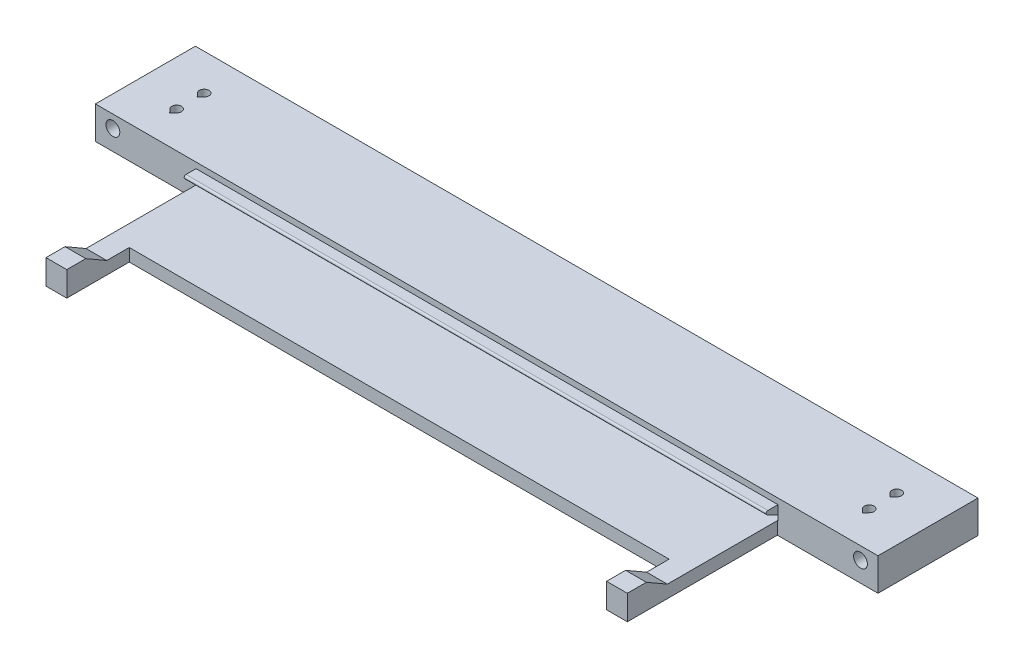
SolidWorks part; units mm, degrees
ref_plane "Front Plane" through (0, 0, 0) normal (0, 0, 1) x (1, 0, 0)
ref_plane "Top Plane" through (0, 0, 0) normal (0, 1, 0) x (1, 0, 0)
ref_plane "Right Plane" through (0, 0, 0) normal (1, 0, 0) x (0, 0, -1)
sketch "Sketch1" plane through (0, 0, 0) normal (1, 0, 0) x (0, 0, -1)
  line L1 (0, 0) -> (40, 0)
  line L2 (0, 0) -> (0, 10)
  line L3 (0, 10) -> (40, 10)
  line L4 (40, 0) -> (40, 10)
  dimension "D1" = 10
  dimension "D2" = 40
extrude "Boss-Extrude1" add sketch "Sketch1" along normal blind 312.998
sketch "Sketch2" plane through (0, 0, -40) normal (0, 0, -1) x (-1, 0, 0)
  line L1 (-272.994, 3) -> (-40.004, 3)
  line L2 (-272.994, 3) -> (-272.994, 4.2)
  line L3 (-272.994, 4.2) -> (-40.004, 4.2)
  line L4 (-40.004, 3) -> (-40.004, 4.2)
  line L5 (-272.994, 4.2) -> (-312.998, 0) construction
  line L6 (-40.004, 4.2) -> (0, 0) construction
  line L7 (-312.998, 0) -> (0, 0) construction
  dimension "D1" = 232.99
  dimension "D2" = 3
  dimension "D3" = 1.2
extrude "Cut-Extrude1" cut sketch "Sketch2" against normal through all
sketch "Sketch3" plane through (0, 10, 0) normal (0, 1, 0) x (1, 0, 0)
  line L0 (156.499, 71.4665) -> (156.499, -49.9307) construction
  line L1 (0, 40) -> (156.499, 71.4665) construction
  line L2 (156.499, 71.4665) -> (312.998, 40) construction
  line L3 (312.998, 40) -> (312.998, 0) construction
  line L4 (312.998, 40) -> (0, 40) construction
  line L5 (312.998, 40) -> (294.998, 25.5) construction
  line L6 (294.998, 25.5) -> (294.998, 14.5) construction
  line L7 (294.998, 14.5) -> (312.998, 0) construction
  circle A0 centre (294.998, 25.5) radius 1.9177
  circle A1 centre (294.998, 14.5) radius 1.9177
  circle A2 centre (18, 14.5) radius 1.9177
  circle A3 centre (18, 25.5) radius 1.9177
  dimension "D3" = 3.8354
  dimension "D1" = 18
  dimension "D2" = 14.5
extrude "Cut-Extrude2" cut sketch "Sketch3" against normal through all
sketch "Sketch4" plane through (0, 0, 0) normal (0, -1, 0) x (1, 0, 0)
  line L1 (14.5837, -12.5276) -> (14.5837, -16.4724)
  line L2 (14.5837, -16.4724) -> (18, -18.4448)
  line L3 (18, -18.4448) -> (21.4163, -16.4724)
  line L4 (21.4163, -16.4724) -> (21.4163, -12.5276)
  line L5 (21.4163, -12.5276) -> (18, -10.5552)
  line L6 (18, -10.5552) -> (14.5837, -12.5276)
  line L7 (14.5837, -23.5276) -> (14.5837, -27.4724)
  line L8 (14.5837, -27.4724) -> (18, -29.4448)
  line L9 (18, -29.4448) -> (21.4163, -27.4724)
  line L10 (21.4163, -27.4724) -> (21.4163, -23.5276)
  line L11 (21.4163, -23.5276) -> (18, -21.5552)
  line L12 (18, -21.5552) -> (14.5837, -23.5276)
  line L13 (298.4143, -12.5276) -> (294.998, -10.5552)
  line L14 (294.998, -10.5552) -> (291.5817, -12.5276)
  line L15 (291.5817, -12.5276) -> (291.5817, -16.4724)
  line L16 (291.5817, -16.4724) -> (294.998, -18.4448)
  line L17 (294.998, -18.4448) -> (298.4143, -16.4724)
  line L18 (298.4143, -16.4724) -> (298.4143, -12.5276)
  line L19 (291.5817, -23.5276) -> (291.5817, -27.4724)
  line L20 (291.5817, -27.4724) -> (294.998, -29.4448)
  line L21 (294.998, -29.4448) -> (298.4143, -27.4724)
  line L22 (298.4143, -27.4724) -> (298.4143, -23.5276)
  line L23 (298.4143, -23.5276) -> (294.998, -21.5552)
  line L24 (294.998, -21.5552) -> (291.5817, -23.5276)
  circle A0 centre (18, -14.5) radius 3.4163 construction
  circle A1 centre (18, -25.5) radius 3.4163 construction
  circle A2 centre (294.998, -14.5) radius 3.4163 construction
  circle A3 centre (294.998, -25.5) radius 3.4163 construction
  dimension "D1" = 6.8326
extrude "Cut-Extrude3" cut sketch "Sketch4" against normal blind 4.3
sketch "Sketch5" plane through (0, 0, 0) normal (0, 0, 1) x (1, 0, 0)
  line L0 (0, 10) -> (7, 5) construction
  line L1 (7, 5) -> (0, 0) construction
  line L2 (0, 10) -> (156.499, 87.0064) construction
  line L3 (156.499, 87.0064) -> (312.998, 10) construction
  line L4 (312.998, 10) -> (312.998, 0) construction
  line L5 (312.998, 10) -> (0, 10) construction
  line L6 (156.499, 87.0064) -> (156.499, -80.9825) construction
  line L7 (305.998, 5) -> (312.998, 0) construction
  line L8 (312.998, 10) -> (305.998, 5) construction
  circle A0 centre (7, 5) radius 2.7623
  circle A1 centre (305.998, 5) radius 2.7623
  dimension "D1" = 5.5245
  dimension "D2" = 7
extrude "Cut-Extrude4" cut sketch "Sketch5" against normal through all
sketch "Sketch6" plane through (0, 0, 0) normal (-1, 0, 0) x (0, 0, 1)
  line L0 (-40, 10) -> (-33, 8.4163) construction
  line L1 (-33, 8.4163) -> (-29, 8.4163)
  line L2 (-33, 8.4163) -> (-33, 1.5837)
  line L3 (-33, 1.5837) -> (-29, 1.5837)
  line L4 (-29, 8.4163) -> (-29, 1.5837)
  line L9 (-33, 1.5837) -> (-40, 0) construction
  line L10 (-40, 10) -> (-20, 18.9404) construction
  line L11 (-20, 18.9404) -> (0, 10) construction
  line L12 (-20, 18.9404) -> (-20, -7.3414) construction
  line L13 (-7, 1.5837) -> (0, 0) construction
  line L14 (0, 10) -> (-7, 8.4163) construction
  line L15 (-11, 8.4163) -> (-11, 1.5837)
  line L16 (-7, 1.5837) -> (-11, 1.5837)
  line L17 (-7, 8.4163) -> (-7, 1.5837)
  line L18 (-7, 8.4163) -> (-11, 8.4163)
  dimension "D1" = 7
  dimension "D2" = 4
  dimension "D3" = 6.8326
extrude "Cut-Extrude5" cut sketch "Sketch6" against normal blind 15
ref_plane "Plane1" through (156.499, 0, 0) normal (-1, 0, 0) x (0, 0, 1)
sketch "Sketch7" plane through (0, 0, 0) normal (0, 0, 1) x (1, 0, 0)
  line L0 (312.998, 0) -> (0, 0) construction
  line L1 (40.249, 0) -> (272.749, 0)
  line L2 (40.249, 0) -> (40.249, 2.0463)
  line L3 (40.249, 2.0463) -> (272.749, 2.0463)
  line L4 (272.749, 0) -> (272.749, 2.0463)
  line L5 (40.249, 2.0463) -> (40.004, 4.2) construction
  line L6 (272.994, 4.2) -> (272.749, 2.0463) construction
  dimension "D1" = 232.5
extrude "Boss-Extrude2" add sketch "Sketch7" along normal blind 60
sketch "Sketch8" plane through (0, 2.0463, 0) normal (0, 1, 0) x (1, 0, 0)
  line L0 (272.749, -60) -> (40.249, -60) construction
  line L1 (48.549, -35) -> (264.449, -35)
  line L2 (48.549, -35) -> (48.549, -60)
  line L3 (48.549, -60) -> (264.449, -60)
  line L4 (264.449, -35) -> (264.449, -60)
  line L5 (48.549, -35) -> (40.249, -60) construction
  line L6 (272.749, -60) -> (264.449, -35) construction
  dimension "D1" = 25
  dimension "D2" = 215.9
extrude "Cut-Extrude6" cut sketch "Sketch8" against normal up to next
sketch "Sketch9" plane through (0, 0, 0) normal (0, -1, 0) x (1, 0, 0)
  line L0 (0, -40) -> (0, 0)
  line L1 (0, 0) -> (40.249, 0)
  line L2 (40.249, 0) -> (40.249, 60)
  line L3 (40.249, 60) -> (48.549, 60)
  line L4 (48.549, 60) -> (48.549, 35)
  line L5 (48.549, 35) -> (264.449, 35)
  line L6 (264.449, 35) -> (264.449, 60)
  line L7 (264.449, 60) -> (272.749, 60)
  line L8 (272.749, 60) -> (272.749, 0)
  line L9 (272.749, 0) -> (312.998, 0)
  line L10 (312.998, 0) -> (312.998, -40)
  line L11 (312.998, -40) -> (0, -40)
  line L12 (21.4163, -16.4724) -> (21.4163, -12.5276) construction
  line L13 (17.9977, -10.5552) -> (14.5825, -12.5296)
  line L14 (14.5825, -12.5296) -> (14.5849, -16.4744)
  line L15 (14.5849, -16.4744) -> (18.0023, -18.4448)
  line L16 (18.0023, -18.4448) -> (21.4175, -16.4704)
  line L17 (21.4175, -16.4704) -> (21.4151, -12.5256)
  line L18 (21.4151, -12.5256) -> (17.9977, -10.5552)
  line L19 (18.0023, -21.5552) -> (14.5849, -23.5256)
  line L20 (14.5849, -23.5256) -> (14.5825, -27.4704)
  line L21 (14.5825, -27.4704) -> (17.9977, -29.4448)
  line L22 (17.9977, -29.4448) -> (21.4151, -27.4744)
  line L23 (21.4151, -27.4744) -> (21.4175, -23.5296)
  line L24 (21.4175, -23.5296) -> (18.0023, -21.5552)
  line L25 (295.0003, -10.5552) -> (291.5828, -12.5256)
  line L26 (291.5828, -12.5256) -> (291.5805, -16.4704)
  line L27 (291.5805, -16.4704) -> (294.9956, -18.4448)
  line L28 (294.9956, -18.4448) -> (298.4131, -16.4744)
  line L29 (298.4131, -16.4744) -> (298.4154, -12.5296)
  line L30 (298.4154, -12.5296) -> (295.0003, -10.5552)
  line L31 (294.9956, -21.5552) -> (291.5805, -23.5296)
  line L32 (291.5805, -23.5296) -> (291.5828, -27.4744)
  line L33 (291.5828, -27.4744) -> (295.0003, -29.4448)
  line L34 (295.0003, -29.4448) -> (298.4154, -27.4704)
  line L35 (298.4154, -27.4704) -> (298.4131, -23.5256)
  line L36 (298.4131, -23.5256) -> (294.9956, -21.5552)
  circle A0 centre (18, -14.5) radius 3.4163 construction
  circle A1 centre (18, -25.5) radius 3.4163 construction
  circle A2 centre (294.998, -14.5) radius 3.4163 construction
  circle A3 centre (294.998, -25.5) radius 3.4163 construction
extrude "Boss-Extrude3" add sketch "Sketch9" along normal blind 3
sketch "Sketch10" plane through (40.249, 0, 0) normal (-1, 0, 0) x (0, 0, 1)
  line L1 (60, 2.0463) -> (42, 2.0463)
  line L2 (60, 2.0463) -> (60, 6.8906)
  line L3 (60, 6.8906) -> (42, 6.8906)
  line L4 (42, 2.0463) -> (42, 6.8906)
  dimension "D1" = 18
extrude "Boss-Extrude4" add sketch "Sketch10" against normal up to surface (8.3 mm away) up to face at (48.549, -0.4768, 47.5)
sketch "Sketch12" plane through (40.249, 0, 0) normal (-1, 0, 0) x (0, 0, 1)
  line L4 (0, 4.2) -> (7, 7.7)
  line L5 (7, 7.7) -> (0, 7.7)
  line L6 (0, 7.7) -> (0, 4.2)
  line L7 (0, 10) -> (0, -3) construction
  dimension "D1" = 7
  dimension "D2" = 3.5
extrude "Boss-Extrude6" add sketch "Sketch12" against normal up to surface (232.745 mm away) up to face at (272.994, 3.6, -20)
fillet "Fillet1" radius 0.7 1 edges at (156.6215, 7.7, 7)
sketch "Sketch15" plane through (0, 2.0463, 0) normal (0, 1, 0) x (1, 0, 0)
  line L1 (264.449, -42) -> (272.749, -42)
  line L2 (264.449, -42) -> (264.449, -60)
  line L3 (264.449, -60) -> (272.749, -60)
  line L4 (272.749, -42) -> (272.749, -60)
  dimension "D1" = 18
extrude "Boss-Extrude8" add sketch "Sketch15" along normal up to surface (4.8443 mm away) up to face at (44.399, 6.8906, 51)
sketch "Sketch16" plane through (0, 10, 0) normal (0, 1, 0) x (1, 0, 0)
  line L0 (0, 40) -> (156.499, 106.783) construction
  line L1 (156.499, 106.783) -> (312.998, 40) construction
  line L2 (156.499, 106.783) -> (156.499, -99.1914) construction
  line L3 (18, 25.5009) -> (18, 14.5009) construction
  line L4 (16.6158, 24.1728) -> (18, 22.7292)
  line L5 (19.3842, 24.1728) -> (18, 22.7292)
  line L6 (16.6158, 13.1728) -> (18, 11.7292)
  line L7 (19.3842, 13.1728) -> (18, 11.7292)
  line L8 (293.6138, 13.1728) -> (294.998, 11.7292)
  line L9 (296.3822, 13.1728) -> (294.998, 11.7292)
  line L10 (293.6138, 24.1728) -> (294.998, 22.7292)
  line L11 (296.3822, 24.1728) -> (294.998, 22.7292)
  circle A0 centre (18, 25.5) radius 1.9177 construction
  arc A1 (16.6158, 24.1728) -> (19.3842, 24.1728) centre (18, 25.5) ccw
  arc A2 (16.6158, 13.1728) -> (19.3842, 13.1728) centre (18, 14.5) ccw
  arc A3 (296.3822, 13.1728) -> (293.6138, 13.1728) centre (294.998, 14.5) cw
  arc A4 (296.3822, 24.1728) -> (293.6138, 24.1728) centre (294.998, 25.5) cw
  dimension "D2" = 2
  dimension "D1" = 2
extrude "Cut-Extrude8" cut sketch "Sketch16" against normal through all
chamfer "Chamfer1" distance 6 angle 60 2 edges at (44.399, 6.8906, 42) (268.599, 6.8906, 42) first distance on face at (44.399, 4.4685, 42) first distance on face at (268.599, 4.4685, 42)
sketch "Sketch17" plane through (0, 3, 0) normal (0, 1, 0) x (1, 0, 0)
  line L1 (40.004, 0) -> (272.994, 0)
  line L2 (40.004, 0) -> (40.004, 40)
  line L3 (40.004, 40) -> (272.994, 40)
  line L4 (272.994, 0) -> (272.994, 40)
extrude "Cut-Extrude9" cut sketch "Sketch17" against normal up to surface (0.9537 mm away) up to face at (156.499, 2.0463, 30.7509)
